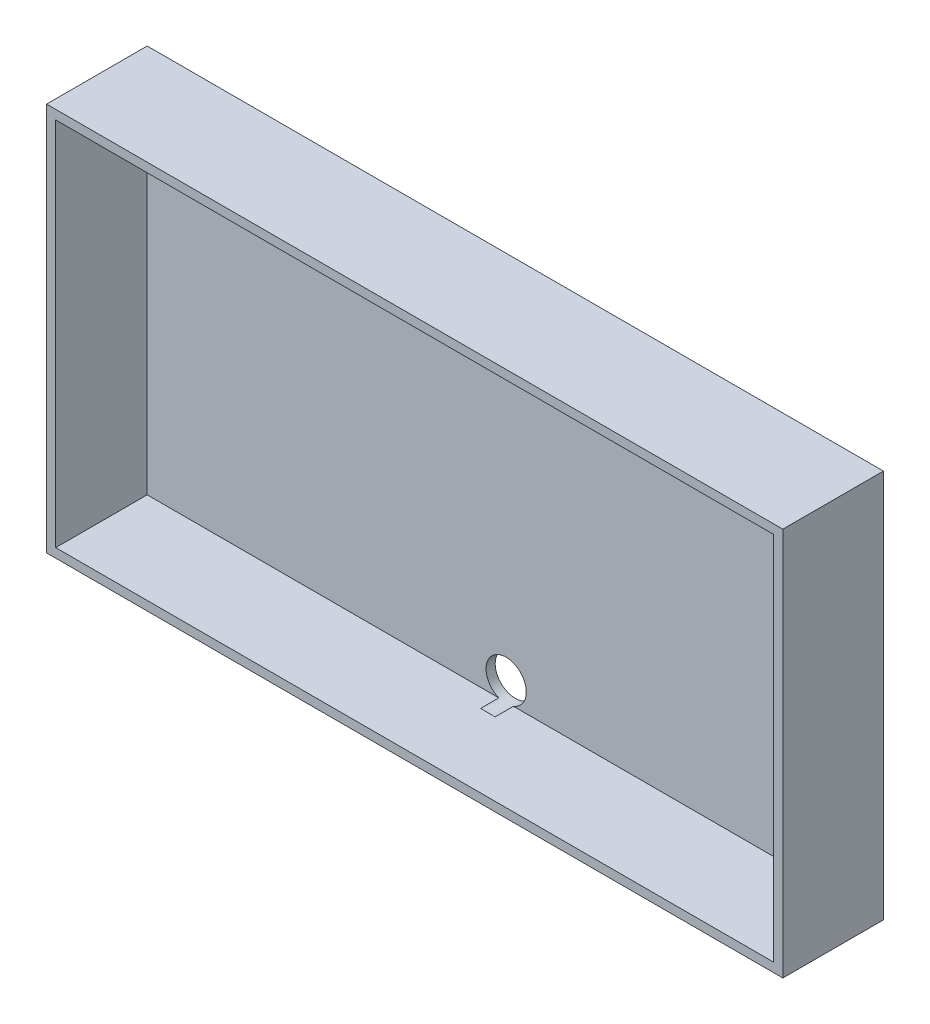
SolidWorks part; units mm, degrees
ref_plane "Front Plane" through (0, 0, 0) normal (0, 0, 1) x (1, 0, 0)
ref_plane "Top Plane" through (0, 0, 0) normal (0, 1, 0) x (1, 0, 0)
ref_plane "Right Plane" through (0, 0, 0) normal (1, 0, 0) x (0, 0, -1)
sketch "Sketch1" plane through (0, 0, 0) normal (0, 0, 1) x (1, 0, 0)
  line L1 (0, 0) -> (80.5, 0)
  line L2 (0, 0) -> (0, -42.5)
  line L3 (0, -42.5) -> (80.5, -42.5)
  line L4 (80.5, 0) -> (80.5, -42.5)
  dimension "D1" = 80.5
  dimension "D2" = 42.5
extrude "Boss-Extrude1" add sketch "Sketch1" along normal blind 11
sketch "Sketch2" plane through (0, 0, 11) normal (0, 0, 1) x (1, 0, 0)
  line L0 (0, 0) -> (0, -42.5) construction
  line L1 (1, -1) -> (79.5, -1)
  line L2 (1, -1) -> (1, -41.5)
  line L3 (1, -41.5) -> (79.5, -41.5)
  line L4 (79.5, -1) -> (79.5, -41.5)
  line L5 (80.5, 0) -> (0, 0) construction
  line L6 (0, -42.5) -> (80.5, -42.5) construction
  line L7 (80.5, -42.5) -> (80.5, 0) construction
  dimension "D1" = 1
  dimension "D2" = 1
  dimension "D3" = 1
  dimension "D4" = 1
extrude "Cut-Extrude1" cut sketch "Sketch2" against normal blind 10
sketch "Sketch3" plane through (0, 0, 0) normal (0, 0, -1) x (-1, 0, 0)
  line L0 (-80.5, -42.5) -> (-80.5, 0) construction
  line L2 (0, -42.5) -> (-80.5, -42.5) construction
  circle A0 centre (-40.25, -39.45) radius 2.2
  circle A1 centre (-40.25, -3.05) radius 2.2
  dimension "D1" = 4.4
  dimension "D2" = 4.4
  dimension "D3" = 32
  dimension "D4" = 40.25
  dimension "D5" = 40.25
  dimension "D6" = 0.85
extrude "Cut-Extrude2" cut sketch "Sketch3" against normal blind 3
